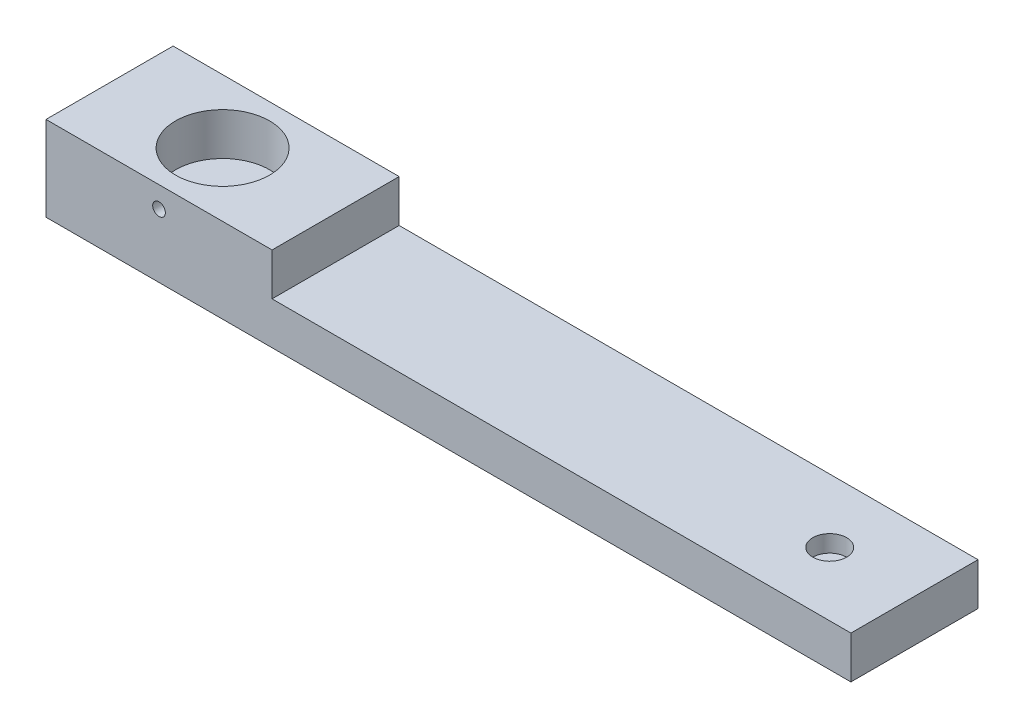
SolidWorks part; units mm, degrees
ref_plane "Front Plane" through (0, 0, 0) normal (0, 0, 1) x (1, 0, 0)
ref_plane "Top Plane" through (0, 0, 0) normal (0, 1, 0) x (1, 0, 0)
ref_plane "Right Plane" through (0, 0, 0) normal (1, 0, 0) x (0, 0, -1)
sketch "Sketch1" plane through (0, 0, 0) normal (0, 1, 0) x (1, 0, 0)
  line L1 (-95, -15) -> (95, -15)
  line L2 (-95, -15) -> (-95, 15)
  line L3 (-95, 15) -> (95, 15)
  line L4 (95, -15) -> (95, 15)
  line L5 (-95, -15) -> (95, 15) construction
  line L6 (-95, 15) -> (95, -15) construction
  point P0 (0, 0)
  dimension "D1" = 190
  dimension "D2" = 30
extrude "Boss-Extrude1" add sketch "Sketch1" along normal blind 10
sketch "Sketch2" plane through (0, 10, 0) normal (0, 1, 0) x (1, 0, 0)
  line L0 (-11, 0) -> (11, 0) construction
  line L2 (-41.6356, -15) -> (-95, -15)
  line L3 (-41.6356, -15) -> (-41.6356, 15)
  line L4 (-41.6356, 15) -> (-95, 15)
  line L5 (-95, -15) -> (-95, 15)
  line L6 (-41.6356, -15) -> (-95, 15) construction
  line L7 (-41.6356, 15) -> (-95, -15) construction
  circle A1 centre (-68.3178, 0) radius 11.1
  line M3 (95, 15) -> (-95, 15)
  line M4 (-95, 15) -> (-95, -15)
  line M5 (-95, -15) -> (95, -15)
  dimension "D2" = 22.2
extrude "Boss-Extrude3" add sketch "Sketch2" along normal blind 10 contours L3 A1 M5 M3 M4 region at (-68.3178, 10, 14.3878)
sketch "Sketch4" plane through (0, 10, 0) normal (0, 1, 0) x (1, 0, 0)
  line L0 (-11, 0) -> (11, 0) construction
  line L1 (95, -15) -> (95, 15) construction
  circle A0 centre (75, 0) radius 4
  dimension "D1" = 8
  dimension "D2" = 20
sketch "Sketch6" plane through (0, 0, 15) normal (0, 0, 1) x (1, 0, 0)
  line L0 (-41.6356, 10) -> (-95, 10) construction
  line L1 (-95, 20) -> (-95, 0) construction
  line L2 (-68.3178, 20) -> (-68.3178, 10) construction
  line L3 (-95, 20) -> (-41.6356, 20) construction
  circle A0 centre (-68.3178, 15) radius 1.5
  dimension "D1" = 3
extrude "Cut-Extrude2" cut sketch "Sketch6" against normal blind 10
extrude "Cut-Extrude3" cut sketch "Sketch4" against normal blind 4
sketch "Sketch7" plane through (0, 6, 0) normal (0, 1, 0) x (1, 0, 0)
  circle A0 centre (75, 0) radius 1.5
  dimension "D1" = 3
extrude "Cut-Extrude4" cut sketch "Sketch7" against normal blind 14
